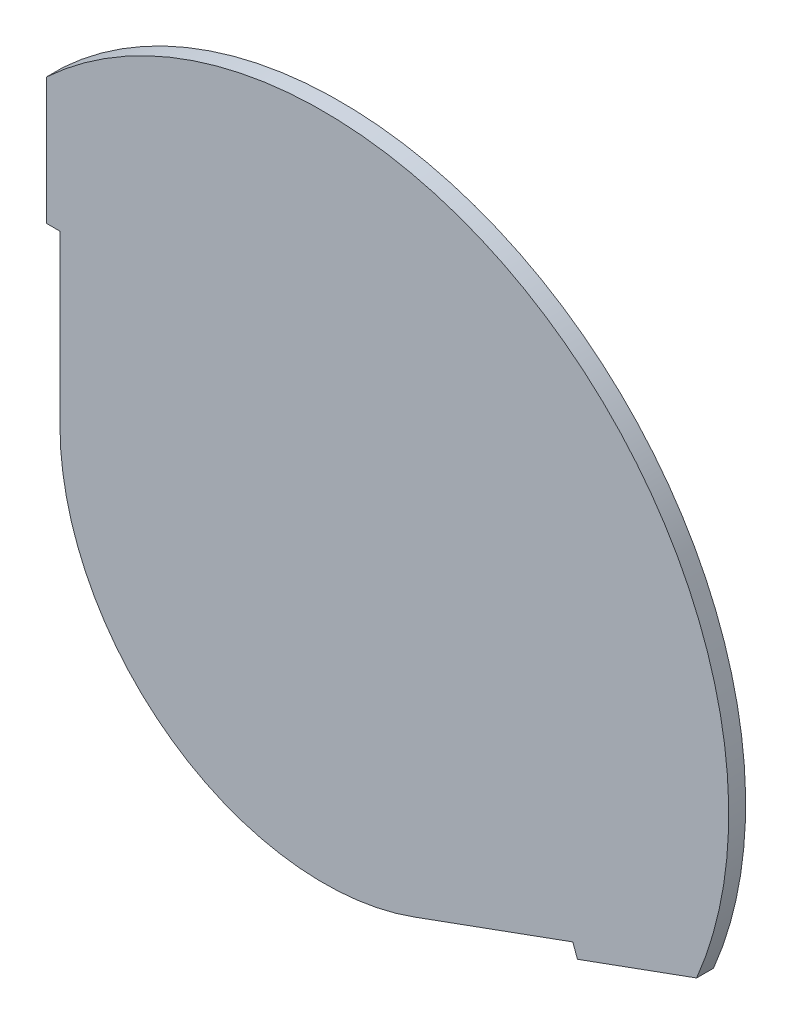
SolidWorks part; units mm, degrees
ref_plane "Front Plane" through (0, 0, 0) normal (0, 0, 1) x (1, 0, 0)
ref_plane "Top Plane" through (0, 0, 0) normal (0, 1, 0) x (1, 0, 0)
ref_plane "Right Plane" through (0, 0, 0) normal (1, 0, 0) x (0, 0, -1)
sketch "Sketch1" plane through (0, 0, 0) normal (0, 0, 1) x (1, 0, 0)
  line L0 (0, 0) -> (-39.624, 0)
  line L1 (0, 0) -> (13.5522, -37.2344)
  line L2 (-39.624, 0) -> (-39.624, 25.4)
  line L3 (13.5522, -37.2344) -> (37.4204, -28.5471)
  line L4 (-39.624, 25.4) -> (-41.656, 25.4)
  line L5 (37.4204, -28.5471) -> (38.1154, -30.4565)
  line L6 (-41.656, 25.4) -> (-41.656, 44.45)
  line L7 (38.1154, -30.4565) -> (56.0165, -23.941)
  arc A0 (-39.624, 0) -> (13.5522, -37.2344) centre (0, 0) ccw
  arc A1 (56.0165, -23.941) -> (-41.656, 44.45) centre (-0.1158, -0.1654) ccw
  point P11 (0, 0)
  point P12 (0, 0)
  point P13 (-14.7393, -21.0499)
  point P14 (0, 0)
  point P15 (4.1588, 5.9394)
  dimension "D1" = 79.248
  dimension "D8" = 60.96
  dimension "D2" = 110
  dimension "D3" = 25.4
  dimension "D4" = 25.4
  dimension "D5" = 2.032
  dimension "D6" = 2.032
  dimension "D7" = 19.05
extrude "Boss-Extrude1" add sketch "Sketch1" along normal blind 2.54 contours L7 A1 L6 L4 L2 L0 L1 L3 L5 | L0 A0 L1 region at (-12.9295, -18.4653, 0) region at (11.9015, 16.997, 0)
